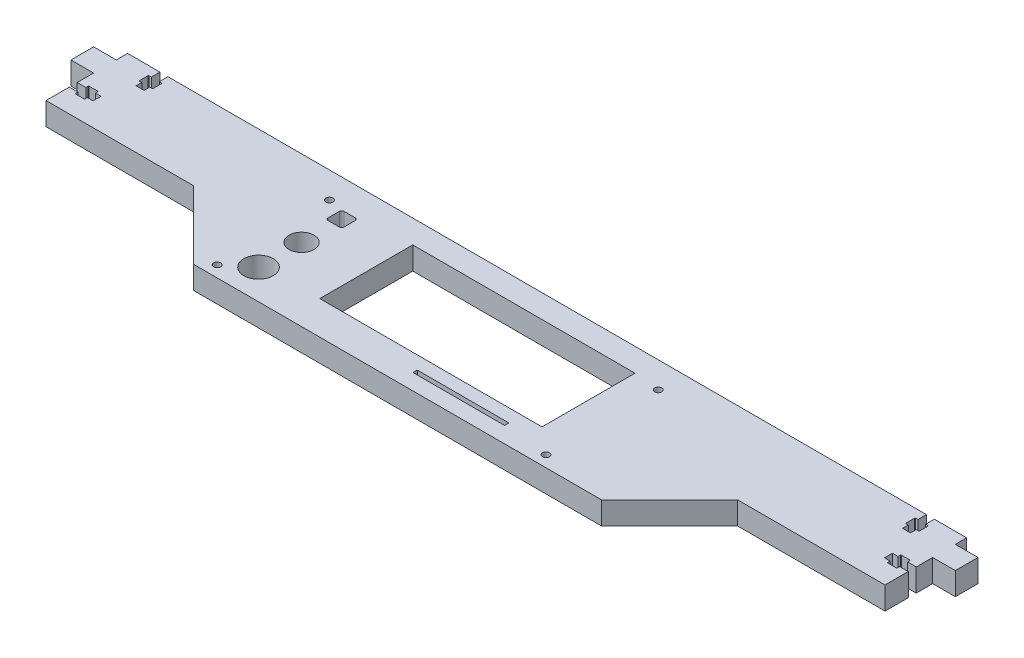
SolidWorks part; units mm, degrees
ref_plane "Front Plane" through (0, 0, 0) normal (0, 0, 1) x (1, 0, 0)
ref_plane "Top Plane" through (0, 0, 0) normal (0, 1, 0) x (1, 0, 0)
ref_plane "Right Plane" through (0, 0, 0) normal (1, 0, 0) x (0, 0, -1)
sketch "Sketch1" plane through (0, 0, 0) normal (0, 1, 0) x (1, 0, 0)
  line L0 (0, 18) -> (0, -18) construction
  line L1 (-185, 18) -> (0, 18)
  line L2 (-185, 18) -> (-185, 13)
  line L3 (-185, -18) -> (0, -18)
  line L4 (0, 18) -> (0, -18)
  line L5 (-185, 18) -> (0, 0) construction
  line L6 (-185, -18) -> (0, 0) construction
  line L7 (-185, 13) -> (-195, 13)
  line L8 (-195, 13) -> (-195, 3)
  line L9 (-195, 3) -> (-185, 3)
  line L10 (-185, 3) -> (-185, -18)
  point P0 (0, 0)
  dimension "D6" = 10
  dimension "D7" = 10
  dimension "D1" = 185
  dimension "D2" = 36
  dimension "D4" = 5
  dimension "D9" = 18
extrude "MainShape" add sketch "Sketch1" along normal blind 10 contours L2 L7 L8 L9 region at (-93.9423, 0, -0.1183)
sketch "Sketch2" plane through (0, 10, 0) normal (0, 1, 0) x (1, 0, 0)
  line L0 (-169, 18) -> (-169, 7.5) construction
  line L1 (-185, 18) -> (0, 18) construction
  line L2 (-170.75, 18) -> (-170.75, 14.2)
  line L3 (-170.75, 14.2) -> (-171.75, 14.2)
  line L4 (-172, 13.95) -> (-172, 10.25)
  line L5 (-171.75, 10) -> (-170.75, 10)
  line L6 (-170.75, 10) -> (-170.75, 7.5)
  line L7 (-170.75, 7.5) -> (-167.25, 7.5)
  line L8 (-185, 18) -> (-185, 13) construction
  line L9 (-170.75, 18) -> (-167.25, 18)
  line L10 (-167.25, 10) -> (-167.25, 7.5)
  line L11 (-166.25, 10) -> (-167.25, 10)
  line L12 (-166, 13.95) -> (-166, 10.25)
  line L13 (-167.25, 14.2) -> (-166.25, 14.2)
  line L14 (-167.25, 18) -> (-167.25, 14.2)
  line L16 (-185, -6) -> (-174.5, -6) construction
  line L50 (-185, 3) -> (-185, -18) construction
  line L51 (-174.5, -7.75) -> (-174.5, -4.25)
  line L52 (-174.5, -4.25) -> (-177, -4.25)
  line L53 (-177, -4.25) -> (-177, -3.25)
  line L54 (-177.25, -3) -> (-180.95, -3)
  line L55 (-181.2, -3.25) -> (-181.2, -4.25)
  line L56 (-181.2, -4.25) -> (-185, -4.25)
  line L57 (-185, -4.25) -> (-185, -7.75)
  line L58 (-195, 13) -> (-195, 3) construction
  line L59 (-181.2, -7.75) -> (-185, -7.75)
  line L60 (-181.2, -8.75) -> (-181.2, -7.75)
  line L61 (-177.25, -9) -> (-180.95, -9)
  line L62 (-177, -7.75) -> (-177, -8.75)
  line L63 (-174.5, -7.75) -> (-177, -7.75)
  arc A0 (-172, 10.25) -> (-171.75, 10) centre (-171.75, 10.25) ccw
  arc A1 (-171.75, 14.2) -> (-172, 13.95) centre (-171.75, 13.95) ccw
  arc A2 (-166.25, 14.2) -> (-166, 13.95) centre (-166.25, 13.95) cw
  arc A3 (-166, 10.25) -> (-166.25, 10) centre (-166.25, 10.25) cw
  arc A16 (-177, -3.25) -> (-177.25, -3) centre (-177.25, -3.25) ccw
  arc A17 (-180.95, -3) -> (-181.2, -3.25) centre (-180.95, -3.25) ccw
  arc A18 (-180.95, -9) -> (-181.2, -8.75) centre (-180.95, -8.75) cw
  arc A19 (-177, -8.75) -> (-177.25, -9) centre (-177.25, -8.75) cw
  point P14 (-172, 10)
  point P17 (-172, 14.2)
  point P28 (-166, 14.2)
  point P29 (-166, 10)
  point P34 (-195, 8)
  point P45 (-177, -3)
  point P48 (-181.2, -3)
  dimension "D8" = 0.25
  dimension "D16" = 0.25
  dimension "D1" = 10.5
  dimension "D2" = 1.75
  dimension "D3" = 1.75
  dimension "D4" = 8
  dimension "D5" = 3
  dimension "D6" = 4.2
  dimension "D7" = 16
  dimension "D9" = 10.5
  dimension "D10" = 8
  dimension "D11" = 4.2
  dimension "D12" = 3
  dimension "D13" = 1.75
  dimension "D14" = 1.75
  dimension "D15" = 14
extrude "ScrewSlots" cut sketch "Sketch2" against normal through all
mirror "Mirror1" about plane through (0, 0, 0) normal (1, 0, 0) of "ScrewSlots", "MainShape"
sketch "Sketch6" plane through (0, 10, 0) normal (0, 1, 0) x (1, 0, 0)
  line L0 (0, -18) -> (0, -48) construction
  line L2 (-185, -18) -> (185, -18) construction
  line L3 (90, -48) -> (-90, -48)
  line L4 (-90, -48) -> (-120, -18)
  line L5 (90, -48) -> (120, -18)
  line L6 (-120, -18) -> (120, -18)
  dimension "D1" = 135
  dimension "D2" = 30
  dimension "D3" = 90
extrude "Boss-Extrude1" add sketch "Sketch6" against normal through all
sketch "Sketch8" plane through (0, 10, 0) normal (0, 1, 0) x (1, 0, 0)
  line L0 (-71.5, 4.8833) -> (-77.5, 4.8833) construction
  line L1 (-77, -1.6167) -> (-72, -1.6167)
  line L2 (-78, -0.6167) -> (-78, 4.3833)
  line L3 (-77, 5.3833) -> (-72, 5.3833)
  line L4 (-71, -0.6167) -> (-71, 4.3833)
  line L5 (-78, -1.6167) -> (-71, 5.3833) construction
  line L6 (-78, 5.3833) -> (-71, -1.6167) construction
  line L7 (-71.5, -1.1167) -> (-71.5, 4.8833) construction
  circle A0 centre (-74.5, -34.7667) radius 6.5
  circle A1 centre (-74.5, -15.8167) radius 5.5
  arc A2 (-77, -1.6167) -> (-78, -0.6167) centre (-77, -0.6167) cw
  circle A3 centre (-74.5, -34.7667) radius 6 construction
  circle A4 centre (-74.5, -15.8167) radius 3.5 construction
  arc A5 (-72, -1.6167) -> (-71, -0.6167) centre (-72, -0.6167) ccw
  arc A6 (-72, 5.3833) -> (-71, 4.3833) centre (-72, 4.3833) cw
  arc A7 (-78, 4.3833) -> (-77, 5.3833) centre (-77, 4.3833) cw
  point P6 (-74.5, 1.8833)
  dimension "D1" = 0.5
  dimension "D2" = 2
  dimension "D3" = 0.5
  dimension "D5" = 1
  dimension "D4" = 0.5
extrude "Cut-Extrude2" cut sketch "Sketch8" against normal through all
sketch "Sketch7" plane through (0, 10, 0) normal (0, 1, 0) x (1, 0, 0)
  circle A0 centre (60.5, -43.0167) radius 1.55
  circle A1 centre (-84.5, -43.0167) radius 1.55
  circle A2 centre (-84.5, 6.4833) radius 1.55
  circle A3 centre (60.5, 6.4833) radius 1.55
  dimension "D1" = 3.1
  dimension "D2" = 3.1
  dimension "D3" = 3.1
  dimension "D4" = 3.1
extrude "Cut-Extrude1" cut sketch "Sketch7" against normal through all
sketch "Sketch9" plane through (0, 10, 0) normal (0, 1, 0) x (1, 0, 0)
  line L0 (0, 7.2333) -> (0, -32.7667) construction
  line L1 (48.5, 7.2333) -> (-48.5, 7.2333) construction
  line L2 (-48.5, -32.7667) -> (48.5, -32.7667) construction
  line L3 (-48.5, -12.7667) -> (48.5, -12.7667) construction
  line L4 (-48.5, 7.2333) -> (-48.5, -32.7667) construction
  line L5 (48.5, -32.7667) -> (48.5, 7.2333) construction
  line L7 (-49, -33.2667) -> (49, -33.2667)
  line L8 (-49, -33.2667) -> (-49, 7.7333)
  line L9 (-49, 7.7333) -> (49, 7.7333)
  line L10 (49, -33.2667) -> (49, 7.7333)
  line L11 (-49, -33.2667) -> (49, 7.7333) construction
  line L12 (-49, 7.7333) -> (49, -33.2667) construction
  point P12 (0, -12.7667)
  dimension "D1" = 0.5
  dimension "D2" = 0.5
extrude "Cut-Extrude3" cut sketch "Sketch9" against normal through all and the other way through all
sketch "Sketch10" plane through (0, 10, 0) normal (0, 1, 0) x (1, 0, 0)
  line L0 (20, -39.2667) -> (20, -40.7667) construction
  line L1 (40, -39.2667) -> (0, -39.2667) construction
  line L2 (0, -40.7667) -> (40, -40.7667) construction
  line L3 (0, -40.0167) -> (40, -40.0167) construction
  line L4 (0, -39.2667) -> (0, -40.7667) construction
  line L5 (40, -40.7667) -> (40, -39.2667) construction
  line L7 (-0.2, -40.9667) -> (40.2, -40.9667)
  line L8 (-0.2, -40.9667) -> (-0.2, -39.0667)
  line L9 (-0.2, -39.0667) -> (40.2, -39.0667)
  line L10 (40.2, -40.9667) -> (40.2, -39.0667)
  line L11 (-0.2, -40.9667) -> (40.2, -39.0667) construction
  line L12 (-0.2, -39.0667) -> (40.2, -40.9667) construction
  point P12 (20, -40.0167)
  dimension "D1" = 0.2
  dimension "D2" = 0.2
extrude "Cut-Extrude4" cut sketch "Sketch10" against normal through all
sketch "Sketch11" [suppressed] plane through (0, 0, 0) normal (0, -1, 0) x (1, 0, 0)
  line L1 (-149.5, -2.5) -> (-167.5, -2.5)
  line L2 (-147.5, -0.5) -> (-147.5, 6.5)
  line L3 (-149.5, 8.5) -> (-167.5, 8.5)
  line L4 (-169.5, -0.5) -> (-169.5, 6.5)
  line L5 (-147.5, -2.5) -> (-169.5, 8.5) construction
  line L6 (-147.5, 8.5) -> (-169.5, -2.5) construction
  line L7 (170.75, -7.5) -> (167.25, -7.5) construction
  line L8 (-174.5, 7.75) -> (-174.5, 4.25) construction
  arc A0 (-147.5, 6.5) -> (-149.5, 8.5) centre (-149.5, 6.5) ccw
  arc A1 (-167.5, 8.5) -> (-169.5, 6.5) centre (-167.5, 6.5) ccw
  arc A2 (-167.5, -2.5) -> (-169.5, -0.5) centre (-167.5, -0.5) cw
  arc A3 (-149.5, -2.5) -> (-147.5, -0.5) centre (-149.5, -0.5) ccw
  point P0 (-158.5, 3)
  dimension "D3" = 2
  dimension "D1" = 22
  dimension "D2" = 11
  dimension "D4" = 5
  dimension "D5" = 5
extrude "LCDCableCutout" [suppressed] cut sketch "Sketch11" against normal through all
equation "\"Y-ROD-SPACING\"=75"
equation "\"Y-BED-OFFSET\"=2"
equation "\"Y-BED-ROD-INSET\"=3.5"
equation "\"T-SLOT-NUT-FILLET-RADIUS\"=0.25"
equation "\"T-SLOT-SCREW-SHAFT-RADIUS\"=1.75"
equation "\"T-SLOT-SCREW-SHAFT-CUTOUT-LENGTH\"=10.5"
equation "\"T-SLOT-NUT-DEPTH\"=4.2"
equation "\"T-SLOT-NUT-WIDTH\"=3"
equation "\"T-SLOT-NUT-END-DISTANCE\"=8"
equation "\"ACRYLIC-TAB-CUTOUT-SIZE\"=\"ACRYLIC-THICKNESS\"+\"ACRYLIC-TAB-TOLERANCE\"*2"
equation "\"ACRYLIC-M3-HOLE\"=3.1"
equation "\"SMOOTHROD-CAP-SCREW-DISTANCE\"=20"
equation "\"D2@Sketch2\"=\"T-SLOT-SCREW-SHAFT-RADIUS\""
equation "\"D1@Sketch2\"=\"T-SLOT-SCREW-SHAFT-CUTOUT-LENGTH\""
equation "\"D6@Sketch2\"=\"T-SLOT-NUT-DEPTH\""
equation "\"D5@Sketch2\"=\"T-SLOT-NUT-WIDTH\""
equation "\"D3@Sketch2\"=\"T-SLOT-SCREW-SHAFT-RADIUS\""
equation "\"D8@Sketch2\"=\"T-SLOT-NUT-FILLET-RADIUS\""
equation "\"D4@Sketch2\"=\"T-SLOT-NUT-END-DISTANCE\""
equation "\"D11@Sketch2\"=\"T-SLOT-NUT-DEPTH\""
equation "\"D10@Sketch2\"=\"T-SLOT-NUT-END-DISTANCE\""
equation "\"D13@Sketch2\"=\"T-SLOT-SCREW-SHAFT-RADIUS\""
equation "\"D14@Sketch2\"=\"T-SLOT-SCREW-SHAFT-RADIUS\""
equation "\"D16@Sketch2\"=\"T-SLOT-NUT-FILLET-RADIUS\""
equation "\"D9@Sketch2\"=\"T-SLOT-SCREW-SHAFT-CUTOUT-LENGTH\""
equation "\"ACRYLIC-TAB-WIDTH\"=\"ACRYLIC-THICKNESS\""
equation "\"D6@Sketch1\"=\"ACRYLIC-TAB-WIDTH\""
equation "\"D7@Sketch1\"=\"ACRYLIC-TAB-WIDTH\""
equation "\"FRAME-WIDTH-INNER\"=370"
equation "\"D1@Sketch1\"=\"FRAME-WIDTH-INNER\"/2"
equation "\"X-ROD-SPACING\"=45"
equation "\"Z-ROD-SPACING\"=17.5"
equation "\"ACRYLIC-THICKNESS\"=10"
equation "\"ACRYLIC-THICKNESS2\"=4.5"
equation "\"NEMA17-HOLE-SPACING\"=31"
equation "\"NEMA17-CENTRAL-CUTOUT\"=22.5"
equation "\"Z-BRACKET-REACH\"=55"
equation "\"TOP-BRACKET-SPACING\"=40"
equation "\"SMOOTHROD-X-LENGTH\"=350"
equation "\"SMOOTHROD-Y-LENGTH\"=350"
equation "\"SMOOTHROD-Z-LENGTH\"=350"
equation "\"SMOOTHROD-TIGHTENING-HEADROOM\"=.25"
equation "\"LEADSCREW-Z-LENGTH\"=300"
equation "\"SCREW-LENGTH-FRAME\"=\"ACRYLIC-THICKNESS\" + 10"
equation "\"SCREW-HEAD-RADIUS\"=6"
equation "\"PRINTED-X-SMOOTHROD-DIAMETER\"=8.2"
equation "\"PRINTED-X-SMOOTHROD-CUTOUT\"=10"
equation "\"PRINTED-X-BASE-HEIGHT\"=10"
equation "\"PRINTED-LM8UU-CUTOUT-SIZE\"=15.25"
equation "\"PRINTED-LM8UU-CUTOUT-LENGTH\"=24.5"
equation "\"PRINTED-X-IDLER-HEIGHT\"=16"
equation "\"PSU-MOUNTING-WIDTH\"=95"
equation "\"PSU-MOUNTING-HEIGHT\"=177"
equation "\"D1@MainShape\"=\"ACRYLIC-THICKNESS\""
equation "\"Y-BELT-TO-ROD-DISTANCE\"=20"
equation "\"SPOOL-HOLDER-ROD-SPACING\"=150"
equation "\"Z-ROD-INSET\"=16"
equation "\"D7@Sketch2\"=\"Z-ROD-INSET\""
equation "\"D1@Sketch7\"=\"ACRYLIC-M3-HOLE\""
equation "\"D2@Sketch7\"=\"ACRYLIC-M3-HOLE\""
equation "\"D3@Sketch7\"=\"ACRYLIC-M3-HOLE\""
equation "\"D4@Sketch7\"=\"ACRYLIC-M3-HOLE\""
equation "\"Y-BED-SCREW-SPACING\"=209"
equation "\"Y-BED-SCREW-CUTOUT-SLOT-HEIGHT\"=2"
equation "\"ACRYLIC-TAB-TOLERANCE\"=.1"
equation "\"SCREW-LENGTH-MOTOR\"=\"ACRYLIC-THICKNESS\" + 5"
equation "\"SCREW-LENGTH-EXTRUDER\"=28"
equation "\"PRINTED-M3-HOLE\"=3.5"
equation "\"PRINTED-M3-NUT-AF\"=6.25"
equation "\"ACRYLIC-X-CARRIAGE-WIDTH\"=55"
equation "\"ACRYLIC-X-CARRIAGE-HEIGHT\"=75"
equation "\"ACRYLIC-X-CARRIAGE-LM8UU-CUTOUT-WIDTH\"=24.25"
equation "\"ACRYLIC-X-CARRIAGE-LM8UU-CUTOUT-HEIGHT\"=11.5"
equation "\"ACRYLIC-X-CARRIAGE-SCREW-SPACING-X\"=15"
equation "\"ACRYLIC-X-CARRIAGE-SCREW-SPACING-Y\"=33"
equation "\"ACRYLIC-X-CARRIAGE-CENTER-TAB-SPACING\"=14"
equation "\"ACRYLIC-X-CARRIAGE-EXTRUDER-OFFSET\"=26"
equation "\"ACRYLIC-X-CARRIAGE-EXTRUDER-ANGLE\"=90"
equation "\"ACRYLIC-X-CARRIAGE-EXTRUDER-SHELF-DEPTH\"=\"ACRYLIC-X-CARRIAGE-EXTRUDER-OFFSET\" + 28"
equation "\"ACRYLIC-X-CARRIAGE-EXTRUDER-BRACE-SPACING\"=23"
equation "\"ACRYLIC-X-CARRIAGE-EXTRUDER-BRACE-TAB-OFFSET\"=20"
equation "\"ACRYLIC-X-CARRIAGE-EXTRUDER-BRACE-HEIGHT\"=35"
equation "\"ACRYLIC-X-CARRIAGE-EXTRUDER-BRACE-SCREW-SPACING\"=22"
equation "\"ACRYLIC-X-CARRIAGE-DUAL-WIDTH-MULTIPLIER\"=1.65"
equation "\"ACRYLIC-X-CARRIAGE-DUAL-HOTEND-SPACING\"=42"
equation "\"ACRYLIC-X-CARRIAGE-DUAL-WIDTH\"=103"
equation "\"ACRYLIC-X-CARRIAGE-DUAL-HOTEND-SEPARATION\"=35"
equation "\"ACRYLIC-X-CARRIAGE-DUAL-MOUNT-PLATE-DEPTH\"=76"
equation "\"ACRYLIC-X-CARRIAGE-DUAL-MOUNT-BRACE-WIDTH\"=45"
equation "\"ACRYLIC-X-CARRIAGE-DUAL-MOUNT-SCREW-WIDTH\"=40"
equation "\"BLOWER-FAN-WIDTH\"=15"
